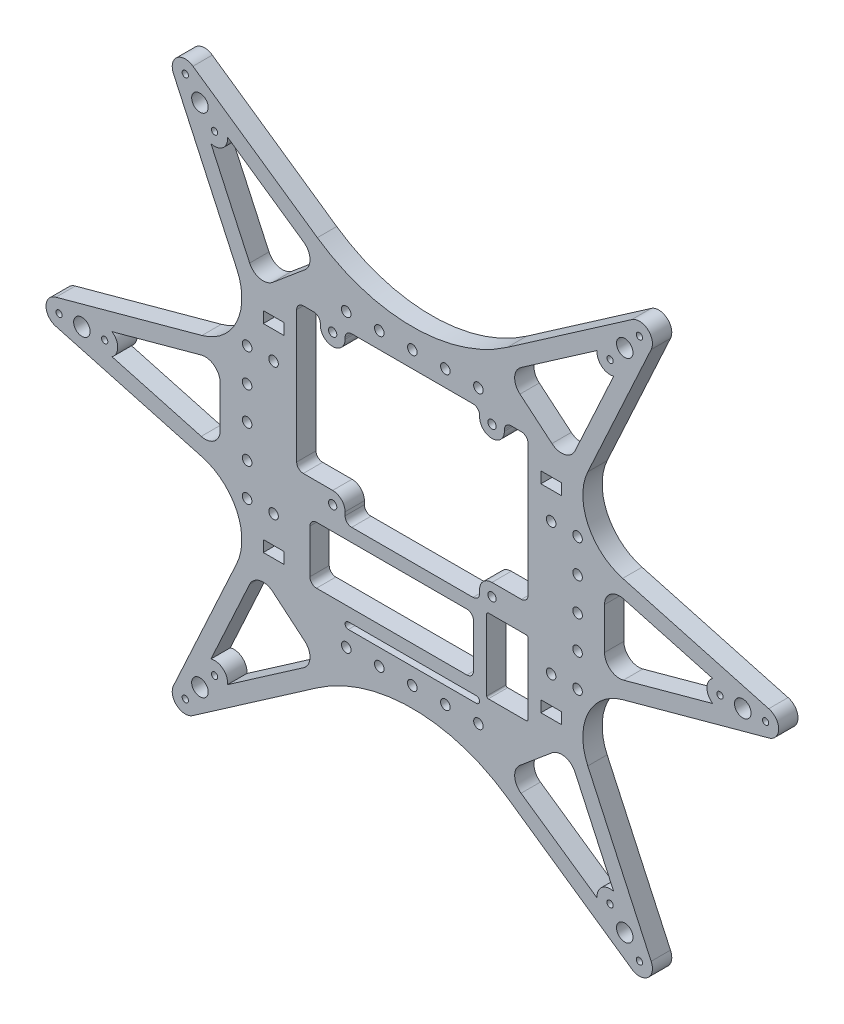
SolidWorks part; units mm, degrees
material "Acrylic (Medium-high impact)"
ref_plane "Front Plane" through (0, 0, 0) normal (0, 0, 1) x (1, 0, 0)
ref_plane "Top Plane" through (0, 0, 0) normal (0, 1, 0) x (1, 0, 0)
ref_plane "Right Plane" through (0, 0, 0) normal (1, 0, 0) x (0, 0, -1)
sketch "Sketch1" plane through (0, 0, 0) normal (0, 0, 1) x (1, 0, 0)
  line L0 (587.1768, 489.0962) -> (587.1768, 412.0041) construction
  line L1 (549.3782, 453.8298) -> (576.3894, 461.205)
  line L2 (582.1207, 456.8289) -> (582.1207, 444.2715)
  line L3 (595.1767, 418.8502) -> (601.3767, 422.2502) construction
  line L4 (595.1767, 422.2502) -> (601.3767, 418.8502) construction
  line L5 (568.9811, 379.8335) -> (581.557, 369.2811) construction
  line L6 (640.2767, 406.5502) -> (630.2767, 406.5502) construction
  line L7 (590.2767, 450.5502) -> (590.2767, 440.5502) construction
  line L8 (-358.708, 400.5502) -> (49641.292, 400.5502) construction
  line L9 (532.4267, 446.7161) -> (532.4267, 454.3842) construction
  line L10 (640.2767, 450.5502) -> (-31503.6634, -37857.1058) construction
  line L11 (704.5554, 373.9457) -> (708.9906, 368.66) construction
  line L12 (704.5554, 373.9457) -> (700.1202, 379.2314) construction
  line L13 (709.6013, 367.9323) -> (706.6642, 365.4678) construction
  line L14 (575.9979, 527.1546) -> (571.5627, 532.4403) construction
  line L15 (575.9979, 527.1546) -> (580.4331, 521.8689) construction
  line L16 (712.5384, 370.3968) -> (709.6013, 367.9323) construction
  line L17 (576.6167, 466.4501) -> (576.6167, 434.6502) construction
  line L18 (663.4579, 422.9239) -> (640.2767, 450.5502) construction
  line L19 (570.952, 533.1681) -> (573.8891, 535.6326) construction
  line L20 (568.0149, 370.3968) -> (570.952, 367.9323) construction
  line L21 (540.2767, 450.5502) -> (547.1767, 450.5502) construction
  line L22 (-351.1587, 450.5502) -> (49648.8413, 450.5502) construction
  line L23 (685.3767, 422.2502) -> (679.1767, 418.8502) construction
  line L24 (685.3767, 418.8502) -> (679.1767, 422.2502) construction
  line L25 (685.3767, 482.2502) -> (679.1767, 478.8502) construction
  line L26 (587.1768, 489.0962) -> (568.0149, 530.7036)
  line L27 (570.952, 367.9323) -> (573.8891, 365.4678) construction
  line L28 (575.9979, 373.9457) -> (580.4331, 379.2314) construction
  line L29 (685.3767, 478.8502) -> (679.1767, 482.2502) construction
  line L30 (611.5369, 509.5368) -> (573.8891, 535.6326)
  line L31 (568.0149, 530.7036) -> (570.952, 533.1681) construction
  line L32 (610.8062, 450.5502) -> (605.2767, 450.5502) construction
  line L33 (605.2767, 489.5502) -> (675.2767, 489.5502)
  line L34 (663.4579, 478.1765) -> (640.2767, 450.5502) construction
  line L35 (540.2767, 450.5502) -> (533.3767, 450.5502) construction
  line L36 (576.6167, 466.4501) -> (532.4267, 454.3842)
  line L37 (575.9979, 373.9457) -> (571.5627, 368.66) construction
  line L38 (595.1767, 422.2502) -> (595.1767, 418.8502)
  line L39 (595.1767, 422.2502) -> (601.3767, 422.2502)
  line L40 (601.3767, 422.2502) -> (601.3767, 418.8502)
  line L41 (640.2767, 450.5502) -> (675.2767, 450.5502) construction
  line L42 (595.1767, 418.8502) -> (601.3767, 418.8502)
  line L43 (731.1751, 447.2706) -> (704.1639, 439.8953)
  line L44 (685.3767, 418.8502) -> (679.1767, 418.8502)
  line L45 (740.2767, 450.5502) -> (747.1767, 450.5502) construction
  line L46 (693.3765, 412.0041) -> (712.5384, 370.3968)
  line L47 (669.7471, 450.5502) -> (675.2767, 450.5502) construction
  line L48 (669.0164, 391.5635) -> (706.6642, 365.4678)
  line L49 (703.9366, 434.6502) -> (748.1267, 446.7161)
  line L50 (712.5384, 530.7036) -> (709.6013, 533.1681) construction
  line L51 (740.2767, 450.5502) -> (733.3767, 450.5502) construction
  line L52 (701.2173, 383.026) -> (689.5047, 408.4585)
  line L53 (696.1927, 378.8099) -> (673.1805, 394.7609)
  line L54 (709.6013, 533.1681) -> (706.6642, 535.6326) construction
  line L55 (672.8516, 401.9043) -> (682.5269, 410.0229)
  line L56 (703.9366, 466.4501) -> (703.9366, 434.6502) construction
  line L57 (679.1767, 422.2502) -> (679.1767, 418.8502)
  line L58 (704.5554, 527.1546) -> (700.1202, 521.8689) construction
  line L59 (704.5554, 527.1546) -> (708.9906, 532.4403) construction
  line L60 (748.1267, 446.7161) -> (748.1267, 454.3842) construction
  line L61 (685.3767, 422.2502) -> (679.1767, 422.2502)
  line L62 (1630.6528, 450.5502) -> (-48369.3472, 450.5502) construction
  line L63 (691.7267, 450.5502) -> (588.8267, 450.5502) construction
  line L64 (607.7017, 401.9043) -> (598.0264, 410.0229)
  line L65 (640.2767, 450.5502) -> (-31503.6634, 38758.2062) construction
  line L66 (584.3606, 378.8099) -> (607.3728, 394.7609)
  line L67 (693.3765, 489.0962) -> (693.3765, 412.0041) construction
  line L68 (-358.708, 500.5502) -> (49641.292, 500.5502) construction
  line L69 (579.336, 518.0744) -> (591.0486, 492.6418)
  line L70 (685.3767, 422.2502) -> (685.3767, 418.8502)
  line L71 (685.3767, 478.8502) -> (685.3767, 482.2502)
  line L72 (605.2767, 489.5502) -> (605.2767, 411.5502)
  line L73 (584.3606, 522.2905) -> (607.3728, 506.3395)
  line L74 (607.7017, 499.196) -> (598.0264, 491.0775)
  line L75 (685.3767, 478.8502) -> (679.1767, 478.8502)
  line L76 (679.1767, 478.8502) -> (679.1767, 482.2502)
  line L77 (672.8516, 499.196) -> (682.5269, 491.0775)
  line L78 (696.1927, 522.2905) -> (673.1805, 506.3395)
  line L79 (675.2767, 489.5502) -> (675.2767, 411.5502)
  line L80 (579.336, 383.026) -> (591.0486, 408.4585)
  line L81 (701.2173, 518.0744) -> (689.5047, 492.6418)
  line L82 (576.6167, 434.6502) -> (532.4267, 446.7161)
  line L83 (605.2767, 411.5502) -> (675.2767, 411.5502)
  line L84 (611.5369, 391.5635) -> (573.8891, 365.4678)
  line L85 (587.1768, 412.0041) -> (568.0149, 370.3968)
  line L86 (549.3782, 447.2706) -> (576.3894, 439.8953)
  line L87 (703.9366, 466.4501) -> (748.1267, 454.3842)
  line L88 (669.0164, 509.5368) -> (706.6642, 535.6326)
  line L89 (693.3765, 489.0962) -> (712.5384, 530.7036)
  line L90 (698.4326, 456.8289) -> (698.4326, 444.2715)
  line L91 (685.3767, 482.2502) -> (679.1767, 482.2502)
  line L97 (731.1751, 453.8298) -> (704.1639, 461.205)
  line L100 (590.2767, 450.5502) -> (590.2767, 460.5502) construction
  line L102 (640.2767, 494.5502) -> (630.2767, 494.5502) construction
  line L104 (568.9811, 521.2669) -> (581.557, 531.8192) construction
  line L111 (640.2767, -48598.7836) -> (640.2767, 49499.884) construction
  line L157 (595.1767, 482.2502) -> (601.3767, 482.2502)
  line L158 (601.3767, 478.8502) -> (601.3767, 482.2502)
  line L159 (595.1767, 478.8502) -> (601.3767, 482.2502) construction
  line L162 (595.1767, 482.2502) -> (601.3767, 478.8502) construction
  line L163 (595.1767, 478.8502) -> (601.3767, 478.8502)
  line L164 (595.1767, 478.8502) -> (595.1767, 482.2502)
  circle A0 centre (533.3767, 450.5502) radius 0.95
  circle A1 centre (598.2767, 430.5502) radius 1.45
  circle A2 centre (575.9979, 527.1546) radius 2.5
  circle A3 centre (547.1767, 450.5502) radius 0.95
  arc A4 (549.3782, 447.2706) -> (549.3782, 453.8298) centre (547.1767, 450.5502) ccw
  circle A5 centre (540.2767, 450.5502) radius 2.5
  arc A6 (532.4267, 446.7161) -> (532.4267, 454.3842) centre (533.3767, 450.5502) cw
  circle A7 centre (590.2767, 460.5502) radius 1.45
  circle A8 centre (571.5627, 532.4403) radius 0.95
  circle A9 centre (580.4331, 521.8689) radius 0.95
  arc A10 (579.336, 518.0744) -> (584.3606, 522.2905) centre (580.4331, 521.8689) ccw
  arc A11 (582.1207, 456.8289) -> (576.3894, 461.205) centre (577.5843, 456.8289) ccw
  circle A12 centre (690.2767, 440.5502) radius 1.45
  circle A13 centre (682.2767, 470.5502) radius 1.45
  circle A14 centre (640.2767, 406.5502) radius 1.45
  arc A15 (568.0149, 530.7036) -> (573.8891, 535.6326) centre (571.5627, 532.4403) cw
  circle A16 centre (690.2767, 430.5502) radius 1.45
  circle A17 centre (704.5554, 373.9457) radius 2.5
  circle A18 centre (708.9906, 368.66) radius 0.95
  circle A19 centre (700.1202, 379.2314) radius 0.95
  circle A20 centre (630.2767, 494.5502) radius 1.45
  circle A21 centre (620.2767, 494.5502) radius 1.45
  arc A22 (701.2173, 383.026) -> (696.1927, 378.8099) centre (700.1202, 379.2314) ccw
  arc A23 (698.4326, 444.2715) -> (704.1639, 439.8953) centre (702.969, 444.2715) ccw
  arc A24 (712.5384, 370.3968) -> (706.6642, 365.4678) centre (708.9906, 368.66) cw
  circle A25 centre (650.2767, 406.5502) radius 1.45
  circle A26 centre (660.2767, 406.5502) radius 1.45
  circle A27 centre (590.2767, 430.5502) radius 1.45
  arc A28 (682.5269, 410.0229) -> (689.5047, 408.4585) centre (685.4185, 406.5767) cw
  arc A29 (672.8516, 401.9043) -> (673.1805, 394.7609) centre (675.7432, 398.4582) ccw
  arc A30 (703.9366, 434.6502) -> (693.3765, 412.0041) centre (708.2497, 418.8538) ccw
  arc A31 (611.5369, 509.5368) -> (669.0164, 509.5368) centre (640.2767, 550.9991) ccw
  arc A34 (576.6167, 434.6502) -> (587.1768, 412.0041) centre (572.3036, 418.8538) cw
  arc A35 (607.7017, 401.9043) -> (607.3728, 394.7609) centre (604.8101, 398.4582) cw
  arc A36 (598.0264, 491.0775) -> (591.0486, 492.6418) centre (595.1348, 494.5236) cw
  arc A37 (607.7017, 499.196) -> (607.3728, 506.3395) centre (604.8101, 502.6422) ccw
  arc A38 (576.6167, 466.4501) -> (587.1768, 489.0962) centre (572.3036, 482.2466) ccw
  arc A39 (598.0264, 410.0229) -> (591.0486, 408.4585) centre (595.1348, 406.5767) ccw
  arc A40 (611.5369, 391.5635) -> (669.0164, 391.5635) centre (640.2767, 350.1012) cw
  circle A41 centre (620.2767, 406.5502) radius 1.45
  circle A42 centre (630.2767, 406.5502) radius 1.45
  arc A43 (568.0149, 370.3968) -> (573.8891, 365.4678) centre (571.5627, 368.66) ccw
  arc A44 (703.9366, 466.4501) -> (693.3765, 489.0962) centre (708.2497, 482.2466) cw
  arc A45 (672.8516, 499.196) -> (673.1805, 506.3395) centre (675.7432, 502.6422) cw
  arc A46 (682.5269, 491.0775) -> (689.5047, 492.6418) centre (685.4185, 494.5236) ccw
  circle A47 centre (682.2767, 430.5502) radius 1.45
  arc A48 (582.1207, 444.2715) -> (576.3894, 439.8953) centre (577.5843, 444.2715) cw
  circle A49 centre (590.2767, 470.5502) radius 1.45
  arc A50 (579.336, 383.026) -> (584.3606, 378.8099) centre (580.4331, 379.2314) cw
  circle A51 centre (580.4331, 379.2314) radius 0.95
  circle A52 centre (571.5627, 368.66) radius 0.95
  circle A53 centre (590.2767, 440.5502) radius 1.45
  circle A54 centre (575.9979, 373.9457) radius 2.5
  circle A58 centre (660.2767, 494.5502) radius 1.45
  circle A59 centre (650.2767, 494.5502) radius 1.45
  arc A63 (712.5384, 530.7036) -> (706.6642, 535.6326) centre (708.9906, 532.4403) ccw
  arc A66 (698.4326, 456.8289) -> (704.1639, 461.205) centre (702.969, 456.8289) cw
  arc A67 (701.2173, 518.0744) -> (696.1927, 522.2905) centre (700.1202, 521.8689) cw
  circle A68 centre (700.1202, 521.8689) radius 0.95
  circle A69 centre (708.9906, 532.4403) radius 0.95
  circle A70 centre (690.2767, 450.5502) radius 1.45
  arc A71 (748.1267, 446.7161) -> (748.1267, 454.3842) centre (747.1767, 450.5502) ccw
  circle A72 centre (740.2767, 450.5502) radius 2.5
  arc A74 (731.1751, 447.2706) -> (731.1751, 453.8298) centre (733.3767, 450.5502) cw
  circle A75 centre (733.3767, 450.5502) radius 0.95
  circle A76 centre (704.5554, 527.1546) radius 2.5
  circle A78 centre (747.1767, 450.5502) radius 0.95
  circle A81 centre (690.2767, 470.5502) radius 1.45
  circle A82 centre (640.2767, 494.5502) radius 1.45
  circle A86 centre (690.2767, 460.5502) radius 1.45
  circle A89 centre (590.2767, 450.5502) radius 1.45
  circle A129 centre (598.2767, 470.5502) radius 1.45
  circle A130 centre (590.2767, 480.5502) radius 1.45 [skipped]
  point P0 (640.2767, 500.5502)
  point P26 (698.4326, 450.5502)
  point P44 (582.1207, 450.5502)
  point P46 (582.1207, 450.5502)
  point P51 (598.2767, 420.5502)
  point P54 (602.8641, 495.1368)
  point P55 (582.9721, 518.843)
  point P64 (582.1207, 450.5502)
  point P74 (693.3765, 450.5502)
  point P82 (703.9366, 450.5502)
  point P97 (576.6167, 450.5502)
  point P104 (640.2767, 489.5502)
  point P110 (587.1768, 450.5502)
  point P124 (602.8641, 495.1368)
  point P191 (640.2767, 400.5502)
  point P192 (569.0236, 365.6342)
  point P199 (640.2767, 411.5502)
  point P200 (677.6892, 405.9636)
  point P201 (602.8641, 405.9636)
  point P202 (582.9721, 382.2573)
  point P229 (677.6892, 495.1368)
  point P231 (698.4326, 450.5502)
  point P238 (640.2767, 489.5502)
  point P242 (569.0236, 535.4662)
  point P307 (640.2767, 500.5502)
  point P366 (598.2767, 480.5502)
  dimension "D6" = 1.9
  dimension "D9" = 42
  dimension "D11" = 5
  dimension "D12" = 13.8
  dimension "D14" = 20
  dimension "D16" = 4
  dimension "D17" = 3
  dimension "D19" = 75
  dimension "D20" = 2.9
  dimension "D13" = 70
  dimension "D27" = 28
  dimension "D8" = 1.9
  dimension "D36" = 3
  dimension "D37" = 3
  dimension "D47" = 5
  dimension "D28" = 3
  dimension "D25" = 3
  dimension "D51" = 39
  dimension "D10" = 10
  dimension "D21" = 44
  dimension "D22" = 13.8
  dimension "D33" = 50
  dimension "D34" = 6.2
  dimension "D35" = 100
  dimension "D41" = 5
  dimension "D43" = 100
  dimension "D44" = 3.4
  dimension "D53" = 10
  dimension "D56" = 10
  dimension "D59" = 5
  dimension "D61" = 28
extrude "Boss-Extrude1" add sketch "Sketch1" along normal blind 5.85
sketch "Sketch2" plane through (0, 0, 5.85) normal (0, 0, 1) x (1, 0, 0)
  line L0 (605.2767, 489.5502) -> (605.2767, 411.5502) construction
  line L1 (675.2767, 411.5502) -> (675.2767, 489.5502) construction
  line L2 (605.2767, 411.5502) -> (675.2767, 411.5502) construction
  line L3 (675.2767, 489.5502) -> (605.2767, 489.5502)
  line L4 (605.2767, 445.6202) -> (605.2767, 411.5502)
  line L5 (616.1717, 487.0802) -> (616.1717, 441.8702) construction
  line L6 (605.2767, 411.5502) -> (619.9217, 411.5502)
  line L7 (529.4267, 450.5502) -> (751.1267, 450.5502) construction
  line L8 (640.2767, 400.5502) -> (640.2767, 500.5502) construction
  line L9 (664.3817, 487.0802) -> (664.3817, 441.8702) construction
  line L10 (616.1717, 487.0802) -> (664.3817, 487.0802) construction
  line L11 (664.3817, 445.6202) -> (675.2767, 445.6202)
  line L12 (660.6317, 489.5502) -> (668.1317, 489.5502)
  line L13 (660.6317, 487.0802) -> (660.6317, 489.5502)
  line L14 (619.9217, 487.0802) -> (619.9217, 489.5502)
  line L15 (619.9217, 489.5502) -> (612.4217, 489.5502)
  line L16 (612.4217, 487.0802) -> (612.4217, 489.5502)
  line L17 (619.3034, 485.0174) -> (612.4217, 489.5502) construction
  line L18 (619.9217, 489.5502) -> (613.0399, 485.0174) construction
  line L19 (661.2499, 485.0174) -> (668.1317, 489.5502) construction
  line L20 (660.6317, 489.5502) -> (667.5134, 485.0174) construction
  line L21 (668.1317, 487.0802) -> (668.1317, 489.5502)
  line L22 (619.9217, 411.5502) -> (619.9217, 413.5502)
  line L23 (616.1717, 445.6202) -> (605.2767, 445.6202)
  line L24 (660.6317, 411.5502) -> (660.6317, 413.5502)
  line L25 (619.9217, 438.8202) -> (660.6317, 438.8202)
  line L26 (660.6317, 411.5502) -> (675.2767, 411.5502)
  line L27 (675.2767, 411.5502) -> (675.2767, 414.5502)
  line L28 (619.9217, 441.8702) -> (619.9217, 438.8202)
  line L29 (660.6317, 441.8702) -> (660.6317, 438.8202)
  line L30 (660.6317, 413.5502) -> (619.9217, 413.5502)
  line L31 (662.7767, 437.0502) -> (675.2767, 437.0502)
  line L32 (662.7767, 414.5502) -> (675.2767, 414.5502)
  line L33 (609.2767, 434.8202) -> (658.7767, 434.8202)
  line L34 (658.7767, 434.8202) -> (658.7767, 417.5502)
  line L35 (662.7767, 437.0502) -> (662.7767, 414.5502)
  line L36 (658.7767, 417.5502) -> (609.2767, 417.5502)
  line L37 (675.2767, 414.5502) -> (675.2767, 437.0502)
  line L38 (609.2767, 417.5502) -> (609.2767, 434.8202)
  line L39 (609.2767, 434.8202) -> (609.2767, 417.5502)
  line L40 (675.2767, 437.0502) -> (675.2767, 445.6202)
  circle A0 centre (616.1717, 487.0802) radius 1.25
  circle A1 centre (664.3817, 487.0802) radius 1.25
  arc A2 (664.3817, 445.6202) -> (660.6317, 441.8702) centre (664.3817, 441.8702) ccw
  circle A3 centre (664.3817, 441.8702) radius 1.25
  arc A4 (619.9217, 487.0802) -> (612.4217, 487.0802) centre (616.1717, 487.0802) cw
  arc A5 (660.6317, 487.0802) -> (668.1317, 487.0802) centre (664.3817, 487.0802) ccw
  arc A6 (616.1717, 445.6202) -> (619.9217, 441.8702) centre (616.1717, 441.8702) cw
  circle A7 centre (616.1717, 441.8702) radius 1.25
  dimension "D1" = 2.47
  dimension "D2" = 3.75
  dimension "D4" = 4
  dimension "D5" = 4
  dimension "D6" = 2
  dimension "D7" = 4
extrude "Boss-Extrude3" add sketch "Sketch2" against normal up to surface (5.85 mm away) separate body contours A4 L14 L3 L16 A0 | L13 A5 L21 L3 A1 | A6 L23 L22 L30 L24 L32 L35 L31 L11 A2 L29 L25 L28 A3 L36 L38 L33 L34 A7 region at (668.0342, 488.3152, 5.85) region at (619.8242, 488.3152, 5.85) region at (610.7242, 444.8417, 5.85) up to face at (598.2767, 480.5502, 0)
combine bodies "Combine1" operation type add bodies to combine 118 119 120 114
fillet "Fillet2" radius 2 1 edges at (619.9217, 438.8202, 2.925)
fillet "Fillet3" radius 2 9 edges at (612.4217, 489.5502, 2.925) (660.6317, 489.5502, 2.925) (668.1317, 489.5502, 2.925) (619.9217, 489.5502, 2.925) (658.7767, 417.5502, 2.925) (609.2767, 417.5502, 2.925) (609.2767, 434.8202, 2.925) (658.7767, 434.8202, 2.925) (660.6317, 438.8202, 2.925)
fillet "Fillet4" radius 0.5 4 edges at (675.2767, 414.5502, 2.925) (662.7767, 414.5502, 2.925) (675.2767, 437.0502, 2.925) (662.7767, 437.0502, 2.925)
fillet "Fillet5" radius 1 4 edges at (660.6317, 411.5502, 2.925) (660.6317, 413.5502, 2.925) (619.9217, 411.5502, 2.925) (619.9217, 413.5502, 2.925)
fillet "Fillet6" radius 2 4 edges at (675.2767, 445.6202, 2.925) (675.2767, 489.5502, 2.925) (605.2767, 489.5502, 2.925) (605.2767, 445.6202, 2.925)
